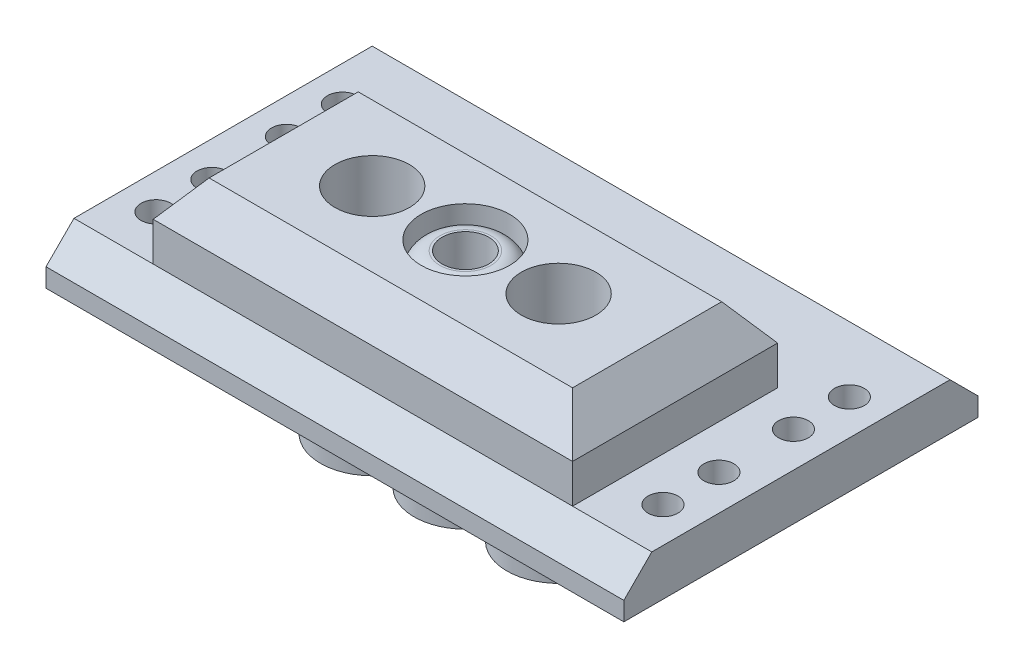
SolidWorks part; units mm, degrees
ref_plane "Alzado" through (0, 0, 0) normal (0, 0, 1) x (1, 0, 0)
ref_plane "Planta" through (0, 0, 0) normal (0, 1, 0) x (1, 0, 0)
ref_plane "Vista lateral" through (0, 0, 0) normal (1, 0, 0) x (0, 0, -1)
sketch "Croquis1" plane through (0, 0, 0) normal (0, 1, 0) x (1, 0, 0)
  line L0 (27.2, -5) -> (27.2, -11) construction
  line L1 (-31, -19) -> (31, -19)
  line L2 (-31, -19) -> (-31, 19)
  line L3 (-31, 19) -> (31, 19)
  line L4 (31, -19) -> (31, 19)
  line L5 (-31, -19) -> (31, 19) construction
  line L6 (-31, 19) -> (31, -19) construction
  line L7 (27.2, -11) -> (-27.2, -11) construction
  line L8 (-27.2, -5) -> (-27.2, -11) construction
  line L9 (27.2, 9) -> (27.2, 3) construction
  line L10 (27.2, 9) -> (27.2, 19) construction
  line L11 (27.2, 9) -> (31, 9) construction
  line L12 (-27.2, 9) -> (-27.2, 3) construction
  line L13 (-27.2, 9) -> (-27.2, 19) construction
  line L14 (0, 0) -> (0, -5) construction
  line L15 (-10, -5) -> (10, -5) construction
  circle A0 centre (27.2, -11) radius 1.6
  circle A1 centre (27.2, -5) radius 1.6
  circle A2 centre (-27.2, -11) radius 1.6
  circle A3 centre (-27.2, -5) radius 1.6
  circle A4 centre (27.2, 9) radius 1.6
  circle A5 centre (27.2, 3) radius 1.6
  circle A6 centre (-27.2, 3) radius 1.6
  circle A7 centre (-27.2, 9) radius 1.6
  circle A8 centre (0, -5) radius 2.5
  circle A9 centre (10, -5) radius 2.55
  circle A10 centre (-10, -5) radius 2.55
  point P0 (0, 0)
  point P31 (0, -5)
  dimension "D4" = 3.2
  dimension "D5" = 3.2
  dimension "D6" = 3.2
  dimension "D7" = 3.2
  dimension "D13" = 3.2
  dimension "D14" = 3.2
  dimension "D20" = 3.2
  dimension "D21" = 3.2
  dimension "D22" = 5
  dimension "D24" = 5.1
  dimension "D25" = 5.1
  dimension "D1" = 62
  dimension "D2" = 38
  dimension "D3" = 6
  dimension "D8" = 6
  dimension "D9" = 54.4
  dimension "D10" = 8
  dimension "D11" = 3.8
  dimension "D12" = 6
  dimension "D15" = 3.8
  dimension "D16" = 10
  dimension "D17" = 6
  dimension "D18" = 10
  dimension "D19" = 3.8
  dimension "D23" = 14
  dimension "D26" = 10
extrude "Saliente-Extruir1" add sketch "Croquis1" along normal blind 5
sketch "Croquis2" plane through (0, 5, 0) normal (0, 1, 0) x (1, 0, 0)
  line L0 (-31, -19) -> (31, -19) construction
  line L1 (0, -5) -> (0, 0) construction
  circle A0 centre (0, -5) radius 4.75
  circle A1 centre (0, -5) radius 2.5
  dimension "D2" = 9.5
  dimension "D3" = 5
  dimension "D1" = 14
extrude "Saliente-Extruir2" add sketch "Croquis2" along normal blind 7
fillet "Redondeo2" radius 2 1 edges at (0, 12, 9.75)
sketch "Croquis4" plane through (0, 5, 0) normal (0, 1, 0) x (1, 0, 0)
  line L0 (0, -5) -> (-10, -5) construction
  line L1 (0, -5) -> (10, -5) construction
  circle A0 centre (10, -5) radius 2.55
  circle A1 centre (-10, -5) radius 2.55
  circle A2 centre (-10, -5) radius 4
  circle A3 centre (10, -5) radius 4
  circle A4 centre (0, -5) radius 2.5 construction
  dimension "D1" = 5.1
  dimension "D2" = 5.1
  dimension "D5" = 8
  dimension "D6" = 8
  dimension "D3" = 10
  dimension "D4" = 10
extrude "Saliente-Extruir3" add sketch "Croquis4" along normal blind 3
fillet "Redondeo3" radius 2 2 edges at (-10, 8, 9) (10, 8, 9)
chamfer "Chaflán1" distance 3 angle 45 2 edges at (0, 5, -19) (0, 5, 19)
sketch "Croquis5" plane through (0, 5, 0) normal (0, 1, 0) x (1, 0, 0)
  line L1 (-22.5, 6) -> (22.5, 6)
  line L2 (-22.5, 6) -> (-22.5, -16)
  line L3 (-22.5, -16) -> (22.5, -16)
  line L4 (22.5, 6) -> (22.5, -16)
  line L5 (-22.5, 6) -> (22.5, -16) construction
  line L6 (-22.5, -16) -> (22.5, 6) construction
  line L7 (-16.5, 2) -> (16.5, 2)
  line L8 (-16.5, 2) -> (-16.5, -12)
  line L9 (-16.5, -12) -> (16.5, -12)
  line L10 (16.5, 2) -> (16.5, -12)
  line L11 (-16.5, 2) -> (16.5, -12) construction
  line L12 (-16.5, -12) -> (16.5, 2) construction
  point P0 (0, -5)
  point P6 (0, -5)
  circle M7 centre (-10, -5) radius 4
  circle M20 centre (0, -5) radius 4.75
  circle M21 centre (10, -5) radius 4
  dimension "D1" = 45
  dimension "D2" = 22
  dimension "D3" = 6
  dimension "D4" = 4
extrude "Saliente-Extruir4" add sketch "Croquis5" along normal blind 8 separate body contours L4 L1 L2 L3 L7 L10 L9 L8 | L8 L9 L7 M20 M7 | L10 L7 L9 M20 M21 region at (0, 5, -5.4991) region at (0, 5, -1.6415)
sketch "Croquis9" plane through (0, 0, 0) normal (0, -1, 0) x (1, 0, 0)
  line L0 (0, -6.6) -> (0, 6.6) construction
  circle A0 centre (0, 5) radius 5.5
  circle A1 centre (0, 5) radius 2.5 construction
  circle A2 centre (10, 5) radius 5.55
  circle A3 centre (10, 5) radius 2.55 construction
  circle A4 centre (-10, 5) radius 5.55
  circle M1 centre (10, 5) radius 2.55
  circle M14 centre (0, 5) radius 2.5
  circle M15 centre (-10, 5) radius 2.55
  dimension "D1" = 3
  dimension "D2" = 3
extrude "Saliente-Extruir7" add sketch "Croquis9" along normal blind 10 contours A0 A2 M1 | A0 A4 A2 M14 | A4 A0 M15 | A0 A2 | A4 A0 region at (4.9745, 0, 5) region at (5.5161, 0, 6.2381) region at (4.3017, 0, 5) region at (-4.9745, 0, 5) region at (-5.6533, 0, 5)
chamfer "Chaflán2" distance 3 angle 52 4 edges at (22.5, 13, 5) (-22.5, 13, 5) (0, 13, -6) (0, 13, 16) first distance on face at (0, 13, 5)
